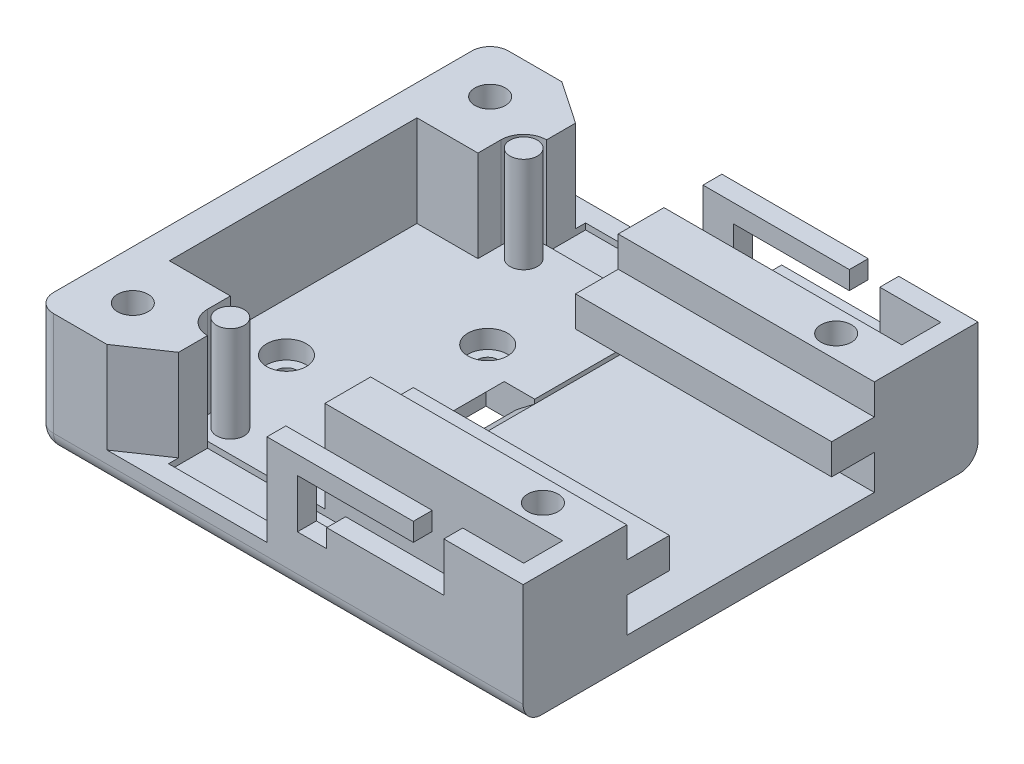
SolidWorks part; units mm, degrees
note: The reader was unsure of these and kept them because the rebuilt part matched: shared geometry of "Sketch2<6>".
ref_plane "Front Plane" through (0, 0, 0) normal (0, 0, 1) x (1, 0, 0)
ref_plane "Top Plane" through (0, 0, 0) normal (0, 1, 0) x (1, 0, 0)
ref_plane "Right Plane" through (0, 0, 0) normal (1, 0, 0) x (0, 0, -1)
sketch "Sketch2" plane through (0, 0, 0) normal (0, 1, 0) x (1, 0, 0)
  line L0 (-5.2561, 19.6424) -> (-5.2561, -0.6576)
  line L1 (-10.2561, -17.6576) -> (69.7439, -17.6576)
  line L2 (-10.2561, -17.6576) -> (-10.2561, 19.6424)
  line L3 (-10.2561, 19.6424) -> (69.7439, 19.6424)
  line L4 (69.7439, -17.6576) -> (69.7439, 19.6424)
  line L5 (-5.2561, -0.6576) -> (69.7439, -0.6576)
  line L6 (4.7439, -0.6576) -> (4.7439, -17.6576)
  line L7 (27.7439, -0.6576) -> (27.7439, -17.6576)
  line L8 (8.4939, -8.1576) -> (8.4939, -17.6576)
  line L9 (8.4939, -12.9076) -> (1.4939, -17.6576)
  line L10 (1.4939, -17.6576) -> (8.4939, -17.6576)
  line L11 (8.4939, -8.1576) -> (66.7439, -8.1576)
  line L12 (66.7439, -8.1576) -> (66.7439, -14.5576)
  line L13 (66.7439, -14.5576) -> (8.4939, -14.5576)
  circle A0 centre (8.4939, -4.4076) radius 3.75
  circle A1 centre (8.4939, -4.4076) radius 2.25
  dimension "D6" = 7.5
  dimension "D7" = 4.5
  dimension "D1" = 17
  dimension "D2" = 80
  dimension "D3" = 5
  dimension "D4" = 15
  dimension "D5" = 42
  dimension "D8" = 20.3
  dimension "D9" = 7
  dimension "D10" = 6.4
  dimension "D11" = 3
extrude "Boss-Extrude1" add sketch "Sketch2" along normal blind 15 contours L12 L13 L7 L1 L4 L5 L11 | A1 | A0 L6 L9 L8 | L9 L6 L5 L0 L3 L2 L1
sketch "Sketch3" plane through (0, 0, 0) normal (0, -1, 0) x (-1, 0, 0)
  line L1 (10.2561, 19.6424) -> (-69.7439, 19.6424)
  line L2 (10.2561, 19.6424) -> (10.2561, -17.6576)
  line L3 (10.2561, -17.6576) -> (-69.7439, -17.6576)
  line L4 (-69.7439, 19.6424) -> (-69.7439, -17.6576)
extrude "Boss-Extrude2" add sketch "Sketch3" along normal blind 3
extrude "Cut-Extrude1" cut sketch "Sketch2<6>" against normal blind 1 contours L13 L7 L11 L8 | L13 L12 L11 L7
sketch "Sketch2<6>" plane through (0, 0, 0) normal (0, 1, 0) x (1, 0, 0) same geometry as "Sketch2"
sketch "Sketch4" plane through (0, 0, 17.6576) normal (0, 0, 1) x (1, 0, 0)
  line L4 (42.5439, 7) -> (66.7439, 7)
  line L5 (66.7439, 7) -> (66.7439, 12)
  line L6 (66.7439, 12) -> (37.4439, 12)
  line L9 (32.7439, 9) -> (32.7439, 4)
  line L10 (51.7439, 12) -> (51.7439, 15)
  line L11 (27.7439, 15) -> (69.7439, 15) construction
  line L12 (51.7439, 15) -> (56.7439, 15)
  line L13 (56.7439, 15) -> (56.7439, 12)
  line L14 (27.7439, 15) -> (27.7439, 0) construction
  line L15 (69.7439, 15) -> (69.7439, -3) construction
  line L16 (56.7439, 12) -> (56.7439, 7)
  line L17 (37.5439, 4) -> (37.5439, 7)
  line L18 (37.5439, 7) -> (42.5439, 7)
  line L19 (37.5439, 4) -> (32.7439, 4)
  line L20 (37.4439, 12) -> (32.7439, 12)
  line L21 (32.7439, 12) -> (32.7439, 9)
  point P24 (56.7439, 13.5)
  dimension "D1" = 5
  dimension "D2" = 4.7
  dimension "D3" = 5
  dimension "D4" = 3
  dimension "D5" = 5
  dimension "D7" = 3
  dimension "D10" = 5
  dimension "D11" = 3
  dimension "D12" = 10
extrude "Cut-Extrude4" cut sketch "Sketch4" against normal up to surface (3.1 mm away)
sketch "Sketch5" plane through (0, 0, 0.6576) normal (0, 0, -1) x (-1, 0, 0)
  line L0 (-69.7439, 15) -> (-69.7439, 0) construction
  line L1 (-69.7439, 10) -> (-27.7439, 10)
  line L2 (-69.7439, 10) -> (-69.7439, 5)
  line L3 (-69.7439, 5) -> (-27.7439, 5)
  line L4 (-27.7439, 10) -> (-27.7439, 5)
  line L5 (-27.7439, 15) -> (-27.7439, 0) construction
  line L6 (-27.7439, 15) -> (-69.7439, 15) construction
  dimension "D1" = 5
  dimension "D2" = 5
extrude "Boss-Extrude3" add sketch "Sketch5" along normal blind 7
sketch "Sketch6" plane through (0, 0, 0) normal (0, 1, 0) x (1, 0, 0)
  line L0 (-5.2561, 19.6424) -> (69.7439, 19.6424) construction
  line L1 (69.7439, -0.6576) -> (29.3439, -0.6576)
  line L2 (69.7439, -0.6576) -> (69.7439, 19.6424)
  line L3 (69.7439, 19.6424) -> (29.3439, 19.6424)
  line L4 (29.3439, -0.6576) -> (29.3439, 19.6424)
  dimension "D1" = 40.4
extrude "Cut-Extrude5" cut sketch "Sketch6" against normal blind 0.7
sketch "Sketch7" plane through (0, 0, -19.6424) normal (0, 0, -1) x (-1, 0, 0)
  line L0 (-29.3439, -0.7) -> (-26.3439, -3)
  line L1 (10.2561, -3) -> (-69.7439, -3) construction
  line L2 (-26.3439, -3) -> (-21.3439, -3)
  line L3 (-21.3439, -3) -> (-24.3439, 0)
  line L4 (5.2561, 0) -> (-29.3439, 0) construction
  line L5 (-24.3439, 0) -> (-29.3439, 0)
  line L6 (-29.3439, 0) -> (-29.3439, -0.7)
  dimension "D1" = 5
  dimension "D2" = 5
  dimension "D3" = 45
extrude "Cut-Extrude6" cut sketch "Sketch7" against normal blind 5
sketch "Sketch8" plane through (0, 15, 0) normal (0, 1, 0) x (1, 0, 0)
  line L0 (-10.2561, -17.6576) -> (-10.2561, 19.6424) construction
  line L1 (-10.2561, -17.6576) -> (1.4939, -17.6576) construction
  line L2 (69.7439, -17.6576) -> (69.7439, -0.6576) construction
  line L3 (27.7439, -0.6576) -> (69.7439, -0.6576) construction
  circle A0 centre (-2.2561, -9.6576) radius 2.5
  circle A1 centre (59.7439, -4.4076) radius 2.5
  dimension "D1" = 5
  dimension "D2" = 8
  dimension "D3" = 8
  dimension "D4" = 10
  dimension "D5" = 3.75
extrude "Cut-Extrude7" cut sketch "Sketch8" against normal blind 5
mirror "Mirror1" about plane through (-10.2561, -3, -19.6424) normal (0, 0, 1) of bodies 112
sketch "Sketch9" plane through (0, 0, 0) normal (0, 1, 0) x (1, 0, 0)
  line L0 (69.7439, 19.5424) -> (-4.5769, 19.5424) construction
  line L1 (17.7439, 10.5424) -> (17.7439, 23.923) construction
  line L2 (-5.2561, 39.9424) -> (-5.2561, -0.6576) construction
  circle A0 centre (17.7439, 28.5424) radius 3.25
  circle A1 centre (17.7439, 10.5424) radius 3.25
  circle A2 centre (2.7439, 10.5424) radius 3.25
  circle A3 centre (17.7439, 10.5424) radius 1.7
  circle A4 centre (17.7439, 28.5424) radius 1.7
  circle A5 centre (2.7439, 10.5424) radius 1.7
  dimension "D1" = 8
  dimension "D2" = 15
  dimension "D3" = 15
  dimension "D4" = 18
extrude "Cut-Extrude8" cut sketch "Sketch9" against normal blind 2
sketch "Sketch10" plane through (0, 0, 0) normal (0, 1, 0) x (1, 0, 0)
  circle A0 centre (17.7439, 28.5424) radius 1.7
  circle A1 centre (17.7439, 10.5424) radius 1.7
  circle A2 centre (2.7439, 10.5424) radius 1.7
extrude "Cut-Extrude10" cut sketch "Sketch10" against normal through all
sketch "Sketch11" plane through (0, 15, 0) normal (0, 1, 0) x (1, 0, 0)
  circle A0 centre (8.4939, -4.4076) radius 2.25
extrude "Boss-Extrude4" add sketch "Sketch11" along normal blind 0.7
sketch "Sketch12" plane through (0, 15, 0) normal (0, 1, 0) x (1, 0, 0)
  circle A0 centre (8.4939, 43.6924) radius 2.25
extrude "Boss-Extrude5" add sketch "Sketch12" along normal blind 0.7
sketch "Sketch13" plane through (0, -3, 0) normal (0, -1, 0) x (-1, 0, 0)
  line L1 (10.2561, -17.6576) -> (-69.7439, -17.6576)
  line L2 (10.2561, -17.6576) -> (10.2561, 56.9424)
  line L3 (10.2561, 56.9424) -> (-69.7439, 56.9424)
  line L4 (-69.7439, -17.6576) -> (-69.7439, 56.9424)
  line L5 (-26.3439, 24.6424) -> (-21.3439, 24.6424)
  line L6 (-26.3439, 24.6424) -> (-26.3439, 14.6424)
  line L7 (-26.3439, 14.6424) -> (-21.3439, 14.6424)
  line L8 (-21.3439, 24.6424) -> (-21.3439, 14.6424)
  circle A0 centre (-17.7439, 28.5424) radius 1.7
  circle A1 centre (-17.7439, 10.5424) radius 1.7
  circle A2 centre (-2.7439, 10.5424) radius 1.7
  dimension "D1" = 3.4
extrude "Boss-Extrude6" add sketch "Sketch13" along normal blind 2
fillet "Fillet1" radius 3 5 edges at (29.7439, -5, 17.6576) (-10.2561, 5, 17.6576) (-10.2561, -5, -19.6424) (-10.2561, 5, -56.9424) (29.7439, -5, -56.9424)
sketch "Sketch14" plane through (0, -2, 0) normal (0, 1, 0) x (1, 0, 0)
  circle A0 centre (17.7439, 28.5424) radius 3.25
  circle A1 centre (17.7439, 10.5424) radius 3.25
  circle A2 centre (2.7439, 10.5424) radius 3.25
extrude "Cut-Extrude11" cut sketch "Sketch14" against normal blind 1
